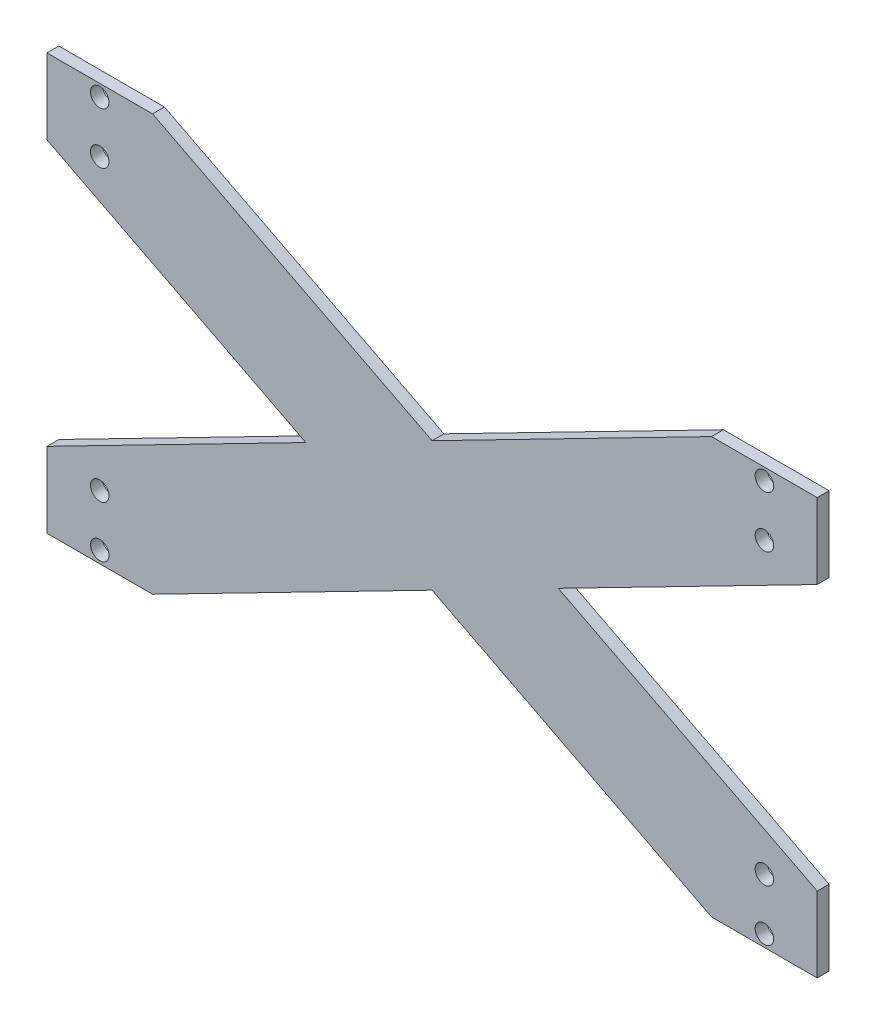
SolidWorks part; units mm, degrees
ref_plane "Front Plane" through (0, 0, 0) normal (0, 0, 1) x (1, 0, 0)
ref_plane "Top Plane" through (0, 0, 0) normal (0, 1, 0) x (1, 0, 0)
ref_plane "Right Plane" through (0, 0, 0) normal (1, 0, 0) x (0, 0, -1)
sketch "Sketch1" plane through (0, 0, 0) normal (0, 0, 1) x (1, 0, 0)
  line L0 (6.342, -12) -> (257.942, -141)
  line L1 (6.342, 16.5) -> (297.942, 16.5)
  line L2 (6.342, 16.5) -> (6.342, -141)
  line L3 (6.342, -141) -> (297.942, -141)
  line L4 (297.942, 16.5) -> (297.942, -141)
  line L5 (297.942, -112.5) -> (46.342, 16.5)
  line L6 (257.942, 16.5) -> (6.342, -112.5)
  line L7 (297.942, -12) -> (46.342, -141)
  circle A0 centre (26.342, 12) radius 3.5
  circle A1 centre (26.342, 12) radius 3.5 construction
  circle A2 centre (26.342, -7.5) radius 3.5
  circle A3 centre (26.342, -7.5) radius 3.5 construction
  circle A4 centre (26.342, -117) radius 3.5
  circle A5 centre (26.342, -136.5) radius 3.5
  circle A6 centre (26.342, -136.5) radius 3.5 construction
  circle A7 centre (26.342, -117) radius 3.5 construction
  circle A8 centre (277.942, 12) radius 3.5
  circle A9 centre (277.942, 12) radius 3.5 construction
  circle A10 centre (277.942, -7.5) radius 3.5
  circle A11 centre (277.942, -7.5) radius 3.5 construction
  circle A12 centre (277.942, -117) radius 3.5
  circle A13 centre (277.942, -117) radius 3.5 construction
  circle A14 centre (277.942, -136.5) radius 3.5
  circle A15 centre (277.942, -136.5) radius 3.5 construction
extrude "Boss-Extrude1" add sketch "Sketch1" along normal blind 4.5 contours L7 L0 L6 L2 L3 A5 A4 | L7 L5 L6 L0 | L6 L5 L1 L2 L0 A2 A0 | L7 L4 L1 L6 L5 A10 A8 | L5 L7 L0 L3 L4 A14 A12 region at (72.2778, -20.8795, 0) region at (152.142, -62.25, 0) region at (72.2778, -103.6205, 0) region at (232.0063, -103.6205, 0) region at (232.0063, -20.8795, 0)
